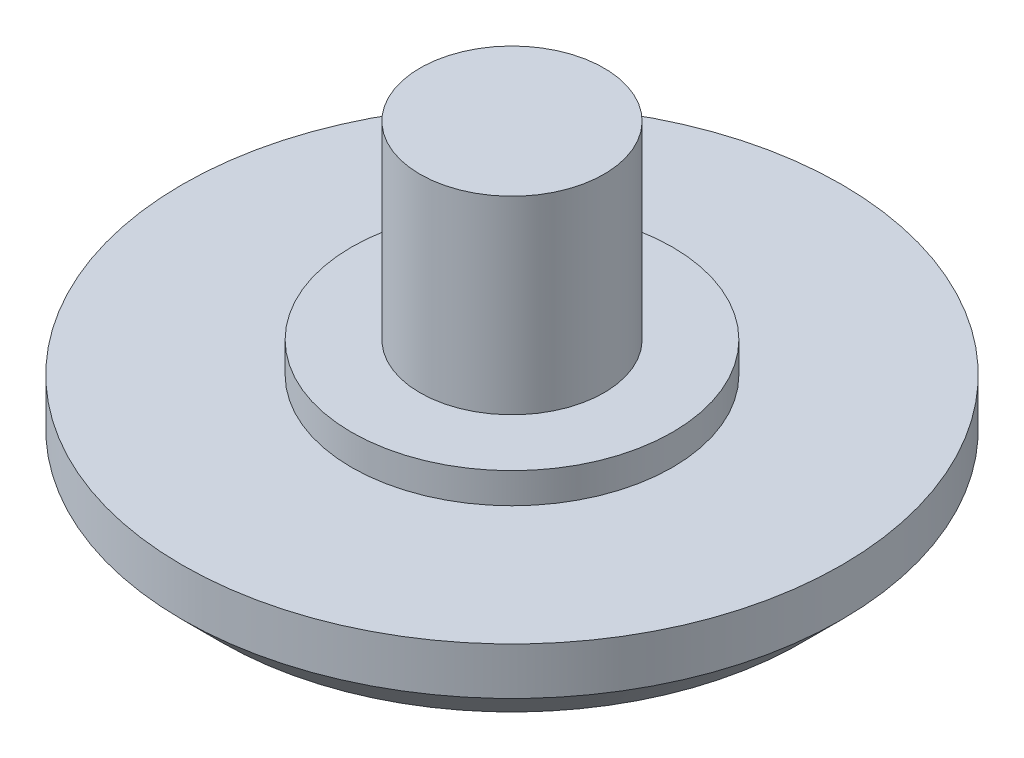
SolidWorks part; units mm, degrees
material "1060 合金"
ref_plane "前视基准面" through (0, 0, 0) normal (0, 0, 1) x (1, 0, 0)
ref_plane "上视基准面" through (0, 0, 0) normal (0, 1, 0) x (1, 0, 0)
ref_plane "右视基准面" through (0, 0, 0) normal (1, 0, 0) x (0, 0, -1)
sketch "草图3" plane through (0, 0, 0) normal (0, 1, 0) x (1, 0, 0)
  circle A1 centre (0, 0) radius 8.24
  dimension "D1" = 16.48
extrude "凸台-拉伸5" add sketch "草图3" along normal blind 2.18 contours A1
sketch "草图7" plane through (0, 2.18, 0) normal (0, 1, 0) x (1, 0, 0)
  circle A0 centre (0, 0) radius 4.01
  dimension "D1" = 8.02
extrude "凸台-拉伸6" add sketch "草图7" along normal blind 1.36
sketch "草图8" plane through (0, 3.54, 0) normal (0, 1, 0) x (1, 0, 0)
  circle A0 centre (0, 0) radius 2.42
extrude "凸台-拉伸7" add sketch "草图8" along normal blind 4.28
sketch "草图9" plane through (0, 0, 0) normal (0, -1, 0) x (1, 0, 0)
  circle A1 centre (0, 0) radius 5.6
  dimension "D1" = 11.2
ref_axis "基准轴1" through (16.2613, 0, 0) along (-1, 0, 0)
extrude "切除-拉伸3" cut sketch "草图9" against normal blind 0.4 contours A1
sketch "草图10" plane through (0, 0, 0) normal (0, 0, 1) x (1, 0, 0)
  line L3 (5.6, 0.4) -> (6.6, 0)
  line L4 (5.6, 0.4) -> (5.6, 0)
  line L5 (5.6, 0) -> (6.6, 0)
  line L6 (16.2613, 0) -> (-1.8667, 0) construction
  dimension "D1" = 0.4
  dimension "D2" = 1
  dimension "D3" = 90
  dimension "D4" = 6.6
  dimension "D5" = 5.6143
revolve "切除-旋转1" cut sketch "草图10" angle 360 about axis through (0, 7.82, 0) along (0, -1, 0)
sketch "草图11" plane through (0, 0, 0) normal (0, 0, 1) x (1, 0, 0)
  line L0 (8.24, 0) -> (8.24, 1)
  line L1 (8.24, 0) -> (8.24, 2.18) construction
  line L2 (8.24, 1) -> (7.24, 0)
  line L3 (7.24, 0) -> (8.24, 0)
  dimension "D1" = 1
  dimension "D2" = 1
revolve "切除-旋转2" cut sketch "草图11" angle 360 about axis through (0, 2.18, 0) along (0, -1, 0)
sketch "草图12" plane through (0, 3.54, 0) normal (0, 1, 0) x (1, 0, 0)
  circle A1 centre (0, 0) radius 4.01
  circle A2 centre (0, 0) radius 4.01
  circle M2 centre (0, 0) radius 2.42
  circle M3 centre (0, 0) radius 4.01
  dimension "D1" = 0
extrude "切除-拉伸5" cut sketch "草图12" against normal blind 0.6 contours M3 M2 region at (-3.8966, 3.54, 0)
sketch "草图13" plane through (0, 7.82, 0) normal (0, 1, 0) x (1, 0, 0)
  circle A0 centre (0, 0) radius 2.3
  dimension "D1" = 4.6
extrude "切除-拉伸6" cut sketch "草图13" against normal up to surface (4.88 mm away) flip side to cut up to face at (0, 2.94, 4.01)
cosmetic thread "装饰螺纹线2" parameters "D1"=4.73, "D2"=3.242
sketch "草图14" plane through (0, 7.82, 0) normal (0, 1, 0) x (1, 0, 0)
  circle A1 centre (0, 0) radius 2.3
  circle A2 centre (0, 0) radius 2.3
  dimension "D1" = 0
extrude "切除-拉伸7" cut sketch "草图14" against normal blind 0.15
